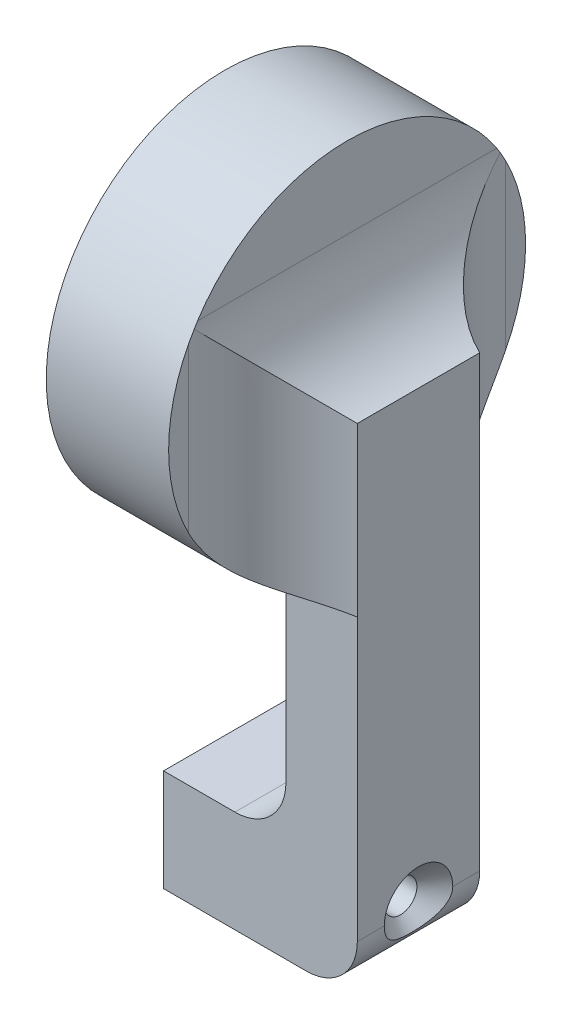
SolidWorks part; units mm, degrees
ref_plane "Front Plane" through (0, 0, 0) normal (0, 0, 1) x (1, 0, 0)
ref_plane "Top Plane" through (0, 0, 0) normal (0, 1, 0) x (1, 0, 0)
ref_plane "Right Plane" through (0, 0, 0) normal (1, 0, 0) x (0, 0, -1)
sketch "Sketch1" plane through (0, 0, 0) normal (0, 0, 1) x (1, 0, 0)
  line L0 (-7, 10) -> (-19, 10)
  line L1 (-19, 10) -> (-19, 0)
  line L2 (-19, 0) -> (0, 0)
  line L3 (0, 0) -> (0, 49)
  line L4 (0, 49) -> (-7, 49)
  line L5 (-7, 49) -> (-7, 10)
  dimension "D1" = 19
  dimension "D2" = 10
  dimension "D3" = 7
  dimension "30" = 49
extrude "Boss-Extrude1" add sketch "Sketch1" along normal blind 12
sketch "Sketch2" plane through (-7, 0, 0) normal (-1, 0, 0) x (0, 0, 1)
  line L0 (12, 49) -> (0, 49) construction
  circle A0 centre (6, 49) radius 9
  dimension "D1" = 18
fillet "Fillet2" radius 5 2 edges at (0, 0, 6) (-7, 10, 6)
hole_wizard "CSK for M3 SFHCS1" positions "Sketch3" profile "Sketch4" countersink size "M3" standard "ANSI Metric"
sketch "Sketch3" plane through (0, 0, 0) normal (1, 0, 0) x (0, 0, -1)
  line L0 (-12, 5) -> (0, 5) construction
  point P0 (-6, 5)
sketch "Sketch4" plane through (0, 5, 6) normal (0, 1, 0) x (0, 0, -1)
  line L0 (0, 0) -> (0, 20.9614)
  line L1 (0, 20.9614) -> (1.6, 20)
  line L2 (1.6, 20) -> (1.6, 1.76)
  line L3 (1.6, 1.76) -> (3.36, 0)
  line L5 (3.36, 0) -> (0, 0)
  line L6 (-1.6, 1.76) -> (-3.36, 0) construction
  line L10 (0, 20.9614) -> (-1.6, 20) construction
  line L11 (0, -6.35) -> (0, 107.95) construction
  dimension "Hole Dia." = 3.2
  dimension "Hole Depth" = 20
  dimension "Near C'Sink Dia." = 6.72
  dimension "Near C'Sink Angle" = 90
  dimension "Drill Angle" = 118
extrude "Boss-Extrude2" add sketch "Sketch2" along normal blind 18
sketch "Sketch5" plane through (-7, 0, 0) normal (1, 0, 0) x (0, 0, -1)
  line L0 (-12, 49) -> (0, 49) construction
  circle A0 centre (-6, 49) radius 17.5
  dimension "D1" = 35
extrude "Boss-Extrude3" add sketch "Sketch5" against normal blind 12
fillet "Fillet3" radius 10 3 edges at (-7, 40.7804, 0) (-7, 49, 6) (-7, 40.7804, 12)
